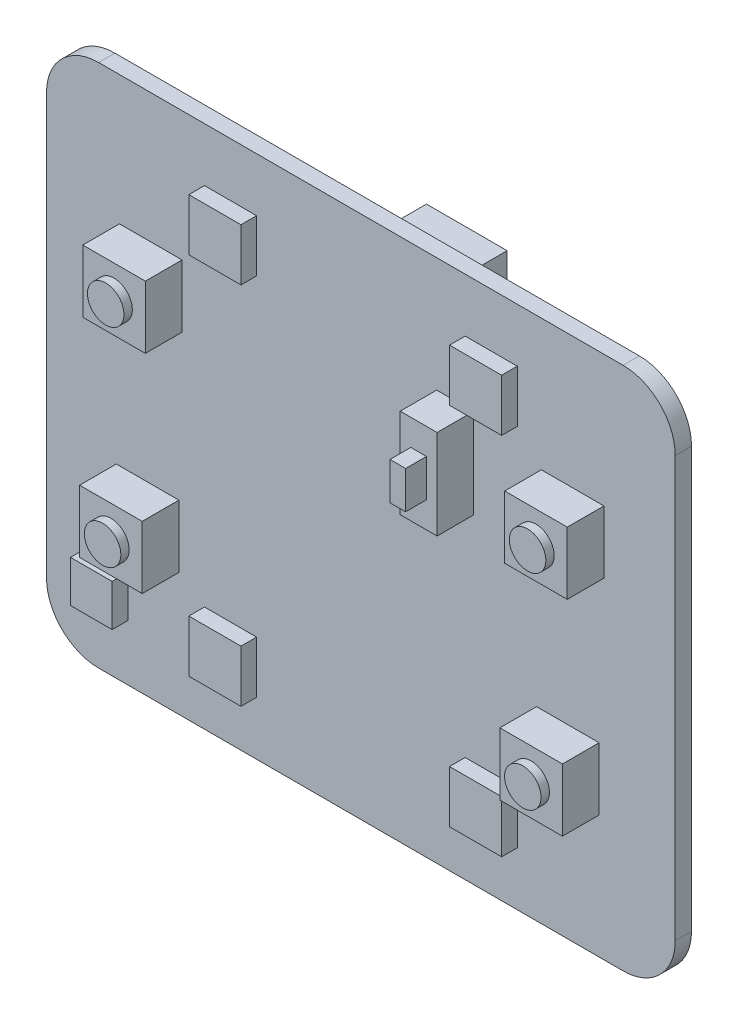
SolidWorks part; units mm, degrees
ref_plane "Plan de face" through (0, 0, 0) normal (0, 0, 1) x (1, 0, 0)
ref_plane "Plan de dessus" through (0, 0, 0) normal (0, 1, 0) x (1, 0, 0)
ref_plane "Plan de droite" through (0, 0, 0) normal (1, 0, 0) x (0, 0, -1)
sketch "Esquisse1" plane through (0, 0, 0) normal (0, 0, 1) x (1, 0, 0)
  line L1 (-25.15, -25.15) -> (25.15, -25.15)
  line L2 (-30.15, -20.15) -> (-30.15, 20.15)
  line L3 (-25.15, 25.15) -> (25.15, 25.15)
  line L4 (30.15, -20.15) -> (30.15, 20.15)
  line L5 (-30.15, -25.15) -> (30.15, 25.15) construction
  line L6 (-30.15, 25.15) -> (30.15, -25.15) construction
  arc A0 (30.15, 20.15) -> (25.15, 25.15) centre (25.15, 20.15) ccw
  arc A1 (25.15, -25.15) -> (30.15, -20.15) centre (25.15, -20.15) ccw
  arc A2 (-30.15, -20.15) -> (-25.15, -25.15) centre (-25.15, -20.15) ccw
  arc A3 (-30.15, 20.15) -> (-25.15, 25.15) centre (-25.15, 20.15) cw
  point P0 (0, 0)
  dimension "D3" = 5
  dimension "D1" = 50.3
  dimension "D2" = 60.3
extrude "PCB" add sketch "Esquisse1" along normal blind 1.56
sketch "Esquisse2" plane through (0, 0, 1.56) normal (0, 0, 1) x (1, 0, 0)
  line L0 (30.15, -20.15) -> (30.15, 20.15) construction
  line L1 (23.31, 12.55) -> (17.31, 12.55)
  line L2 (23.31, 12.55) -> (23.31, 6.55)
  line L3 (23.31, 6.55) -> (17.31, 6.55)
  line L4 (17.31, 12.55) -> (17.31, 6.55)
  line L5 (23.31, 12.55) -> (17.31, 6.55) construction
  line L6 (23.31, 6.55) -> (17.31, 12.55) construction
  line L7 (25.15, 25.15) -> (-25.15, 25.15) construction
  line L8 (-25.15, -25.15) -> (25.15, -25.15) construction
  line L9 (16.85, -7.35) -> (22.85, -7.35)
  line L10 (16.85, -7.35) -> (16.85, -13.35)
  line L11 (16.85, -13.35) -> (22.85, -13.35)
  line L12 (22.85, -7.35) -> (22.85, -13.35)
  line L13 (16.85, -7.35) -> (22.85, -13.35) construction
  line L14 (16.85, -13.35) -> (22.85, -7.35) construction
  line L15 (-23.45, -7.35) -> (-17.45, -7.35)
  line L16 (-23.45, -7.35) -> (-23.45, -13.35)
  line L17 (-23.45, -13.35) -> (-17.45, -13.35)
  line L18 (-17.45, -7.35) -> (-17.45, -13.35)
  line L19 (-23.45, -7.35) -> (-17.45, -13.35) construction
  line L20 (-23.45, -13.35) -> (-17.45, -7.35) construction
  line L21 (-23.15, 12.75) -> (-17.15, 12.75)
  line L22 (-23.15, 12.75) -> (-23.15, 6.75)
  line L23 (-23.15, 6.75) -> (-17.15, 6.75)
  line L24 (-17.15, 12.75) -> (-17.15, 6.75)
  line L25 (-23.15, 12.75) -> (-17.15, 6.75) construction
  line L26 (-23.15, 6.75) -> (-17.15, 12.75) construction
  line L27 (-30.15, 20.15) -> (-30.15, -20.15) construction
  line L28 (0.858, 0) -> (-0.858, 0) construction
  line L29 (7.27, 14.15) -> (10.81, 14.15)
  line L30 (7.27, 14.15) -> (7.27, 5.55)
  line L31 (7.27, 5.55) -> (10.81, 5.55)
  line L32 (10.81, 14.15) -> (10.81, 5.55)
  line L33 (8.29, 11.65) -> (9.79, 11.65)
  line L34 (8.29, 11.65) -> (8.29, 8.05)
  line L35 (8.29, 8.05) -> (9.79, 8.05)
  line L36 (9.79, 11.65) -> (9.79, 8.05)
  line L37 (8.29, 11.65) -> (9.79, 8.05) construction
  line L38 (8.29, 8.05) -> (9.79, 11.65) construction
  line L39 (-12.5, 17.5) -> (12.5, 17.5) construction
  line L40 (-12.5, 17.5) -> (-12.5, -17.5) construction
  line L41 (-12.5, -17.5) -> (12.5, -17.5) construction
  line L42 (12.5, 17.5) -> (12.5, -17.5) construction
  line L43 (-12.5, 17.5) -> (12.5, -17.5) construction
  line L44 (-12.5, -17.5) -> (12.5, 17.5) construction
  line L45 (-15, 15) -> (-10, 15)
  line L46 (-15, 15) -> (-15, 20)
  line L47 (-15, 20) -> (-10, 20)
  line L48 (-10, 15) -> (-10, 20)
  line L49 (-15, 15) -> (-10, 20) construction
  line L50 (-15, 20) -> (-10, 15) construction
  line L51 (-10, -15) -> (-10, -20)
  line L52 (-15, -15) -> (-10, -15)
  line L53 (-15, -15) -> (-15, -20)
  line L54 (-15, -20) -> (-10, -20)
  line L55 (0, -0.858) -> (0, 0.858) construction
  line L56 (10, -15) -> (10, -20)
  line L57 (15, -20) -> (10, -20)
  line L58 (15, -15) -> (15, -20)
  line L59 (15, -15) -> (10, -15)
  line L60 (10, 15) -> (10, 20)
  line L61 (15, 15) -> (10, 15)
  line L62 (15, 15) -> (15, 20)
  line L63 (15, 20) -> (10, 20)
  circle A0 centre (20.31, 9.55) radius 1.75
  circle A1 centre (-20.15, 9.75) radius 1.75
  circle A2 centre (-20.45, -10.35) radius 1.75
  circle A3 centre (19.85, -10.35) radius 1.75
  point P0 (20.31, 9.55)
  point P11 (19.85, -10.35)
  point P16 (-20.45, -10.35)
  point P21 (-20.15, 9.75)
  point P40 (9.04, 9.85)
  point P46 (9.04, 14.15)
  point P47 (0, 0)
  dimension "D4" = 3.5
  dimension "D1" = 6
  dimension "D2" = 6.84
  dimension "D3" = 12.6
  dimension "D5" = 7.3
  dimension "D6" = 11.8
  dimension "D7" = 11.8
  dimension "D8" = 6.7
  dimension "D9" = 12.4
  dimension "D10" = 7
  dimension "D11" = 3.54
  dimension "D12" = 8.6
  dimension "D13" = 6.5
  dimension "D14" = 11
  dimension "D15" = 1.5
  dimension "D16" = 2.5
  dimension "D17" = 35
  dimension "D18" = 25
  dimension "D19" = 5
  dimension "D20" = 2.5
extrude "CorpsBp" add sketch "Esquisse2" along normal blind 3.52 contours L24 L21 L22 L23 A1 | L18 L15 L16 L17 A2 | L1 L4 L3 L2 A0 | L12 L9 L10 L11 A3 | A2 | A1 | A0 | A3 region at (23.2251, 9.55, 1.56) region at (19.85, -7.4349, 1.56) region at (-20.45, -7.4349, 1.56) region at (-20.15, 12.6651, 1.56) region at (20.31, 9.55, 1.56) region at (-20.15, 9.75, 1.56) region at (-20.45, -10.35, 1.56) region at (19.85, -10.35, 1.56)
extrude "BpBp" add sketch "Esquisse2<3>" along normal blind 4.32 contours A2 | A1 | A0 | A3
sketch "Esquisse2<3>" plane through (0, 0, 1.56) normal (0, 0, 1) x (1, 0, 0) same geometry as "Esquisse2"
extrude "CorpsOnOff" add sketch "Esquisse2<4>" along normal blind 3.5 contours L30 L31 L32 L29
sketch "Esquisse2<4>" plane through (0, 0, 1.56) normal (0, 0, 1) x (1, 0, 0) same geometry as "Esquisse2"
extrude "BpOnOff" add sketch "Esquisse2<5>" along normal blind 5.5 contours L35 L36 L33 L34
sketch "Esquisse2<5>" plane through (0, 0, 1.56) normal (0, 0, 1) x (1, 0, 0) same geometry as "Esquisse2"
extrude "Boss.-Extru.9" add sketch "Esquisse2<6>" along normal blind 1.5 contours L47 L48 L45 L46 | L63 L60 L61 L62 | L53 L54 L51 L52 | L57 L56 L59 L58
sketch "Esquisse2<6>" plane through (0, 0, 1.56) normal (0, 0, 1) x (1, 0, 0) same geometry as "Esquisse2"
sketch "Esquisse5" plane through (0, 0, 0) normal (0, 0, -1) x (-1, 0, 0)
  line L1 (-30.15, -20.15) -> (-30.15, 20.15) construction
  line L2 (9.0619, 3.25) -> (15.15, 3.25)
  line L3 (9.0619, -3.35) -> (15.15, -3.35)
  line L4 (25.15, -25.15) -> (-25.15, -25.15) construction
  line L5 (-25.15, 25.15) -> (25.15, 25.15) construction
  line L6 (3.87, 18.95) -> (-3.87, 18.95)
  line L7 (3.87, 18.95) -> (3.87, 13.95)
  line L8 (3.87, 13.95) -> (-3.87, 13.95)
  line L9 (-3.87, 18.95) -> (-3.87, 13.95)
  line L10 (3.87, 18.95) -> (-3.87, 13.95) construction
  line L11 (3.87, 13.95) -> (-3.87, 18.95) construction
  line L12 (15.15, 3.25) -> (15.15, -3.35)
  line L13 (30.15, 20.15) -> (30.15, -20.15) construction
  circle A0 centre (0.75, -18.69) radius 5.9
  arc A1 (9.0619, 3.25) -> (9.0619, -3.35) centre (-1.85, -0.05) ccw
  point P6 (0, 16.45)
  dimension "D1" = 11.8
  dimension "D2" = 25
  dimension "D3" = 0.56
  dimension "D7" = 22.8
  dimension "D8" = 13.8
  dimension "D9" = 16.9
  dimension "D4" = 7.74
  dimension "D5" = 5
  dimension "D6" = 6.2
  dimension "D10" = 6.6
  dimension "D11" = 15
extrude "Buzzer" add sketch "Esquisse5" along normal blind 9.9 contours A0
extrude "ISP" add sketch "Esquisse5<4>" along normal blind 8.6 contours L8 L9 L6 L7
sketch "Esquisse5<4>" plane through (0, 0, 0) normal (0, 0, -1) x (-1, 0, 0) same geometry as "Esquisse5"
extrude "CR2032" add sketch "Esquisse5<5>" along normal blind 7 contours A1 L3 L12 L2
sketch "Esquisse5<5>" plane through (0, 0, 0) normal (0, 0, -1) x (-1, 0, 0) same geometry as "Esquisse5"
sketch "Esquisse6" plane through (0, 0, 1.56) normal (0, 0, 1) x (1, 0, 0)
  line L0 (-30.15, 20.15) -> (-30.15, -20.15) construction
  line L1 (-26.35, -15.8) -> (-22.35, -15.8)
  line L2 (-26.35, -15.8) -> (-26.35, -19.8)
  line L3 (-26.35, -19.8) -> (-22.35, -19.8)
  line L4 (-22.35, -15.8) -> (-22.35, -19.8)
  line L5 (-26.35, -15.8) -> (-22.35, -19.8) construction
  line L6 (-26.35, -19.8) -> (-22.35, -15.8) construction
  line L7 (-25.15, -25.15) -> (25.15, -25.15) construction
  point P0 (-24.35, -17.8)
  dimension "D1" = 3.8
  dimension "D2" = 5.35
  dimension "D3" = 4
extrude "Boss.-Extru.10" add sketch "Esquisse6" along normal blind 1.5
